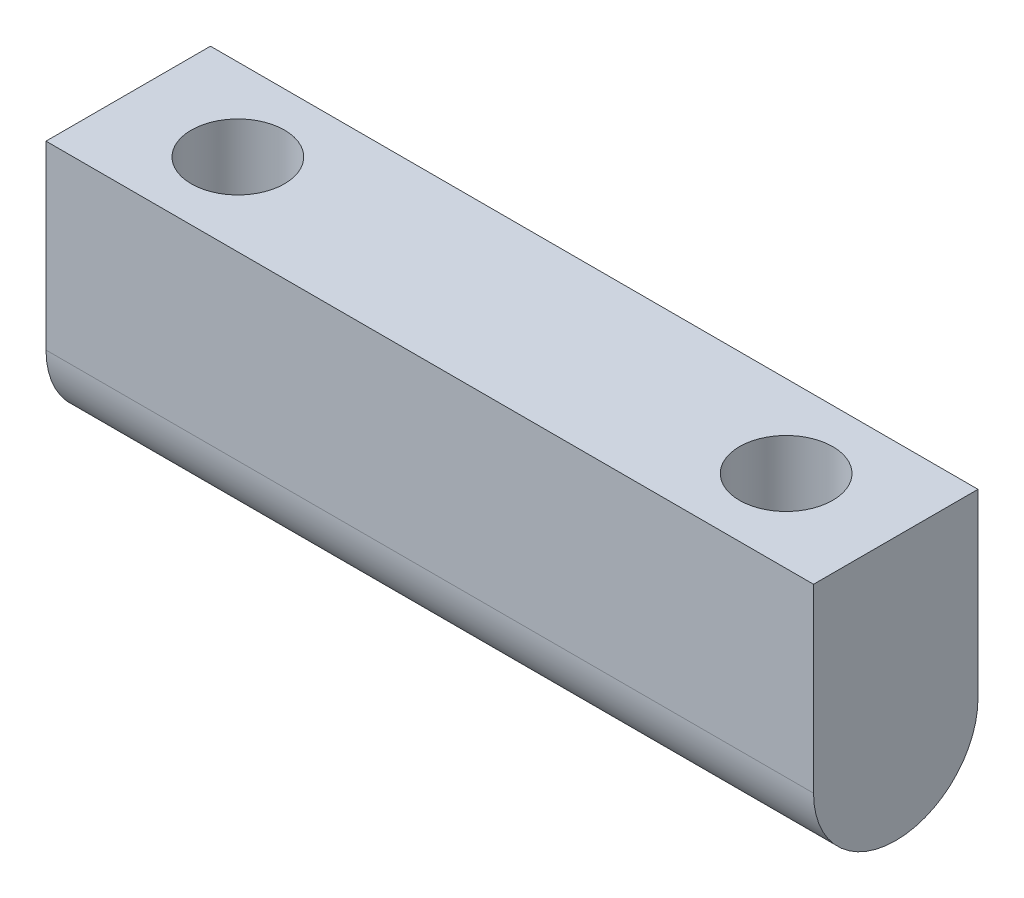
SolidWorks part; units mm, degrees
ref_plane "Front Plane" through (0, 0, 0) normal (0, 0, 1) x (1, 0, 0)
ref_plane "Top Plane" through (0, 0, 0) normal (0, 1, 0) x (1, 0, 0)
ref_plane "Right Plane" through (0, 0, 0) normal (1, 0, 0) x (0, 0, -1)
sketch "Sketch1" plane through (0, 0, 0) normal (0, 1, 0) x (1, 0, 0)
  line L1 (35, -7.5) -> (-35, -7.5)
  line L2 (35, -7.5) -> (35, 7.5)
  line L3 (35, 7.5) -> (-35, 7.5)
  line L4 (-35, -7.5) -> (-35, 7.5)
  line L5 (35, -7.5) -> (-35, 7.5) construction
  line L6 (35, 7.5) -> (-35, -7.5) construction
  circle A0 centre (-25, 0) radius 4.25
  circle A1 centre (25, 0) radius 4.25
  point P0 (0, 0)
  dimension "D5" = 8.5
  dimension "D1" = 15
  dimension "D2" = 70
  dimension "D3" = 25
  dimension "D4" = 25
extrude "Boss-Extrude1" add sketch "Sketch1" along normal blind 20
sketch "Sketch2" plane through (0, 0, 0) normal (0, -1, 0) x (1, 0, 0)
  line L1 (35, -7.5) -> (-35, -7.5)
  line L2 (35, -7.5) -> (35, 7.5)
  line L3 (35, 7.5) -> (-35, 7.5)
  line L4 (-35, -7.5) -> (-35, 7.5)
  line L5 (35, -7.5) -> (-35, 7.5) construction
  line L6 (35, 7.5) -> (-35, -7.5) construction
  point P0 (0, 0)
extrude "Boss-Extrude2" add sketch "Sketch2" along normal blind 4
fillet "Fillet1" radius 7.5 2 edges at (0, -4, 7.5) (0, -4, -7.5)
chamfer "Chamfer1" distance 10 angle 1 2 edges at (25, 0, 4.25) (-25, 0, 4.25) first distance on face at (25, 20, 4.25) first distance on face at (-25, 20, 4.25)
